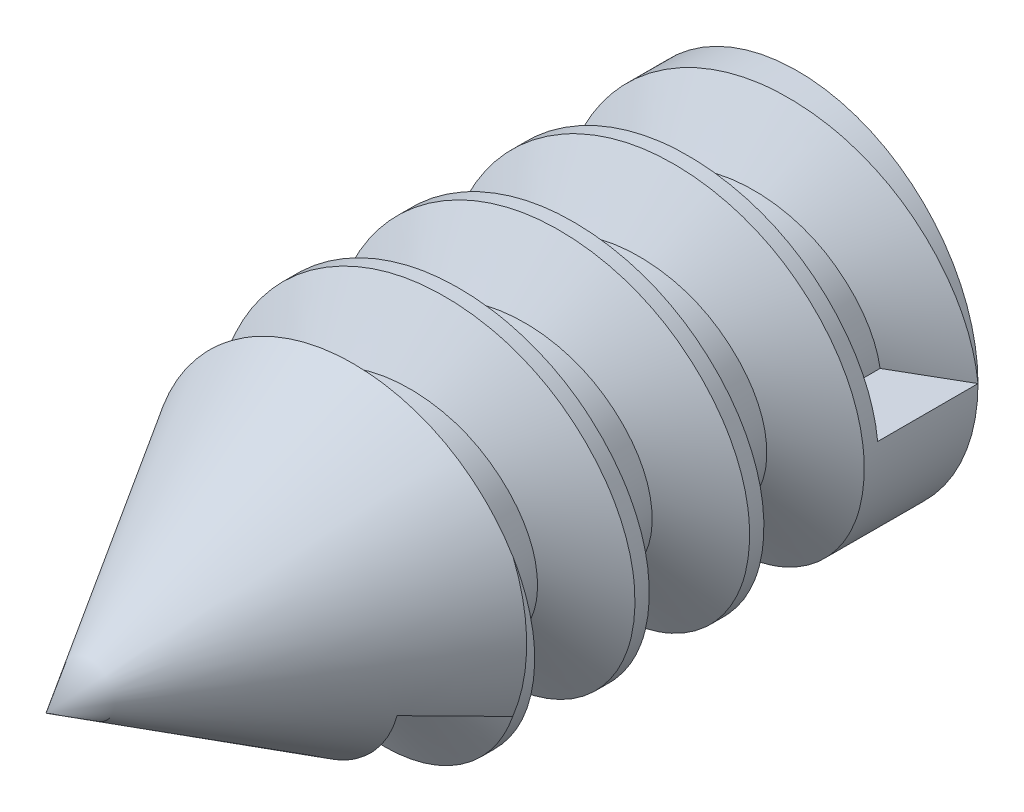
SolidWorks part; units mm, degrees
ref_plane "前视基准面" through (0, 0, 0) normal (0, 0, 1) x (1, 0, 0)
ref_plane "上视基准面" through (0, 0, 0) normal (0, 1, 0) x (1, 0, 0)
ref_plane "右视基准面" through (0, 0, 0) normal (1, 0, 0) x (0, 0, -1)
sketch "草图1" plane through (0, 0, 0) normal (0, 0, 1) x (1, 0, 0)
  circle A0 centre (0, 0) radius 2
extrude "凸台-拉伸1" add sketch "草图1" along normal blind 5 contours A0
sketch "草图2" plane through (0, 0, 0) normal (1, 0, 0) x (0, 0, -1)
  line L0 (-5, 0) -> (-8.3253, 0)
  line L1 (-5, 2) -> (-5, -2) construction
  line L2 (-8.3253, 0) -> (-5, 2)
  line L3 (-5, 2) -> (-5, 0)
revolve "旋转1" add sketch "草图2" angle 360 about L0
thread "螺纹线1" pitch 1.27 method cut profile "螺纹线轮廓1" start angle 0, offset 0, length 0, pitch 1.27, diameter 4
ref_plane "基准面1" through (2, 0, 0) normal (0, -1, 0) x (1, 0, 0)
sketch "螺纹线轮廓1" plane through (2, 0, 0) normal (0, -1, 0) x (1, 0, 0)
  line L0 (0, 0) -> (0, 1.27) construction
  line L11 (0, 0) -> (0, 1.1112)
  line L12 (0, 1.1112) -> (-0.6874, 0.7144)
  line L13 (-0.6874, 0.7144) -> (-0.6874, 0.3969)
  line L15 (-0.6874, 0.3969) -> (0, 0)
  line L17 (-0.6874, 0.5556) -> (0, 0.5556) construction
  point P2 (0, 0)
  dimension "Pitch" = 1.27
  dimension "Profile_Angle" = 60
  dimension "Profile_Land" = 0.3175
  dimension "Profile_Height" = 0.6874
